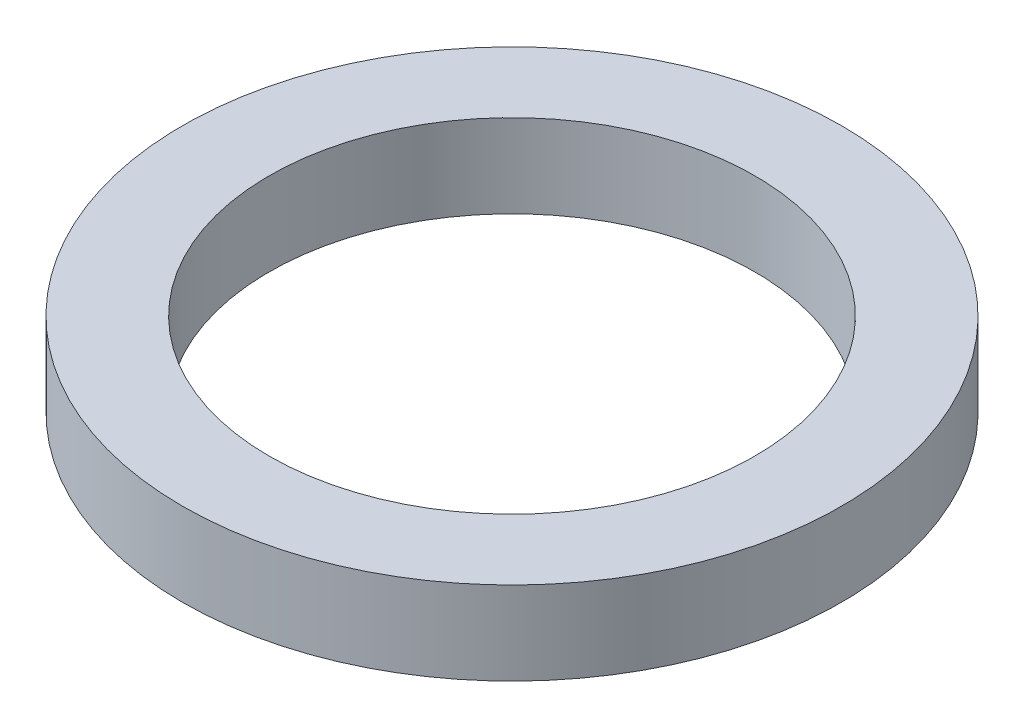
SolidWorks part; units mm, degrees
ref_plane "Front Plane" through (0, 0, 0) normal (0, 0, 1) x (1, 0, 0)
ref_plane "Top Plane" through (0, 0, 0) normal (0, 1, 0) x (1, 0, 0)
ref_plane "Right Plane" through (0, 0, 0) normal (1, 0, 0) x (0, 0, -1)
sketch "Sketch1" plane through (0, 0, 0) normal (0, 1, 0) x (1, 0, 0)
  circle A0 centre (0, 0) radius 47.5
  dimension "FLANGE_OD" = 95
extrude "Boss-Extrude1" add sketch "Sketch1" along normal blind 12
sketch "Sketch2" plane through (0, 0, 0) normal (0, 1, 0) x (1, 0, 0)
  circle A0 centre (0, 0) radius 35
  dimension "BORE_D" = 70
extrude "Cut-Extrude1" cut sketch "Sketch2" along normal through all
sketch "Sketch3" plane through (0, 12, 0) normal (0, 1, 0) x (1, 0, 0)
  circle A0 centre (0, 0) radius 20.7939 construction
  circle A1 centre (-20.7939, 0) radius 1.7666
  dimension "BOLT_D" = 3.5332
  dimension "BOLT_PCD" = 41.5877
extrude "Cut-Extrude2" cut sketch "Sketch3" against normal blind 11.3629 rebuild error yes
pattern_circular "CirPattern1" count 5 over 360 rebuild error yes
